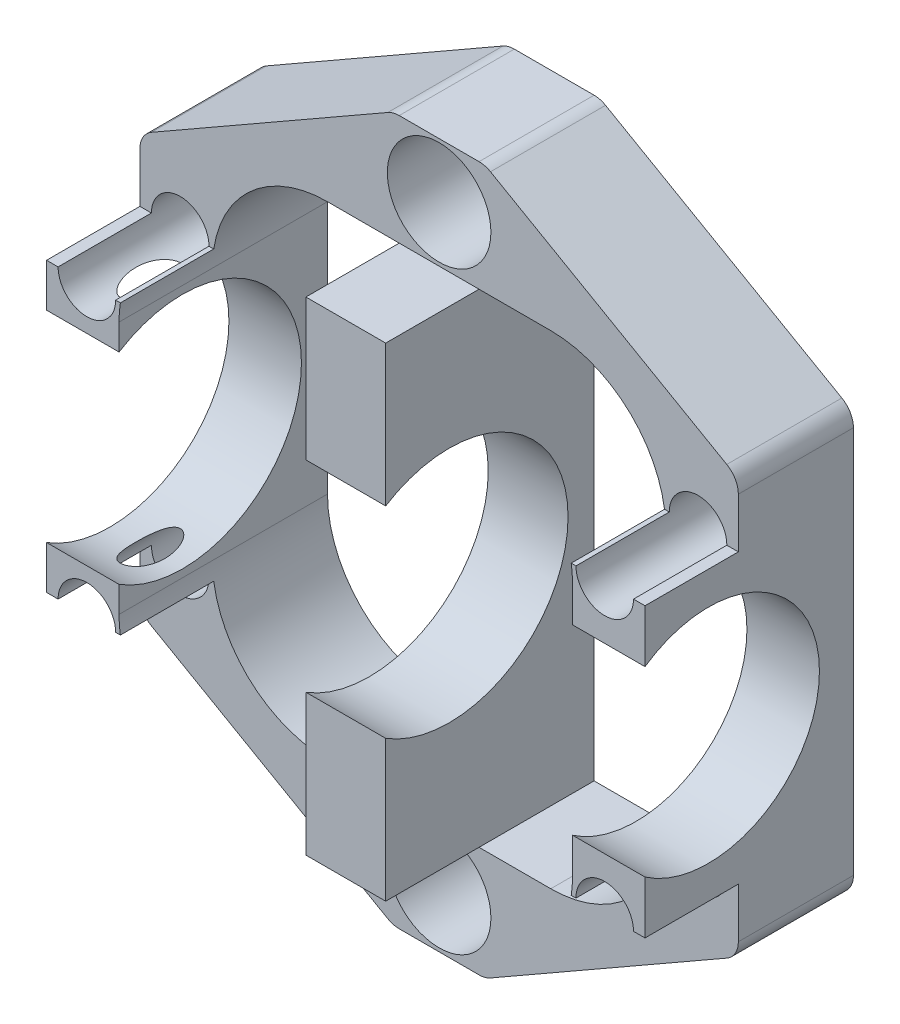
SolidWorks part; units mm, degrees
ref_plane "Front Plane" through (0, 0, 0) normal (0, 0, 1) x (1, 0, 0)
ref_plane "Top Plane" through (0, 0, 0) normal (0, 1, 0) x (1, 0, 0)
ref_plane "Right Plane" through (0, 0, 0) normal (1, 0, 0) x (0, 0, -1)
sketch "Sketch1" plane through (0, 0, 0) normal (0, 0, 1) x (1, 0, 0)
  line L0 (31.75, 34.925) -> (-31.75, 34.925) construction
  line L1 (-44.45, 22.225) -> (-44.45, -22.225) construction
  line L2 (-31.75, -34.925) -> (31.75, -34.925) construction
  line L3 (44.45, -22.225) -> (44.45, 22.225) construction
  line L4 (5.6665, -38.5261) -> (31.7424, -23.5917) construction
  line L5 (-33.02, -21.3876) -> (-33.02, 21.3876) construction
  line L6 (-31.7424, -23.5917) -> (-5.6665, -38.5261) construction
  line L7 (-4.4041, -38.862) -> (4.4041, -38.862) construction
  line L8 (33.02, -21.3876) -> (33.02, 21.3876) construction
  line L9 (5.6665, 38.5261) -> (31.7424, 23.5917) construction
  line L10 (-4.4041, 38.862) -> (4.4041, 38.862) construction
  line L11 (-5.6665, 38.5261) -> (-31.7424, 23.5917) construction
  line L12 (-33.02, -21.3876) -> (-33.02, 21.3876) construction
  line L13 (-33.02, -21.3876) -> (-33.02, 21.3876)
  line L14 (-5.6665, 38.5261) -> (-31.7424, 23.5917)
  line L15 (-4.4041, 38.862) -> (4.4041, 38.862)
  line L16 (5.6665, 38.5261) -> (31.7424, 23.5917)
  line L17 (33.02, -21.3876) -> (33.02, 21.3876)
  line L18 (-4.4041, -38.862) -> (4.4041, -38.862)
  line L19 (-31.7424, -23.5917) -> (-5.6665, -38.5261)
  line L20 (5.6665, -38.5261) -> (31.7424, -23.5917)
  line L21 (44.45, -22.225) -> (44.45, 22.225)
  line L22 (-31.75, -34.925) -> (31.75, -34.925)
  line L23 (-44.45, 22.225) -> (-44.45, -22.225)
  line L24 (31.75, 34.925) -> (-31.75, 34.925)
  line L25 (-12.319, 26.67) -> (12.319, 26.67) construction
  line L26 (25.019, 13.97) -> (25.019, -13.97) construction
  line L27 (-25.019, 13.97) -> (-25.019, -13.97) construction
  line L28 (-12.319, -26.67) -> (12.319, -26.67) construction
  line L29 (-12.319, 26.67) -> (12.319, 26.67)
  line L30 (25.019, 13.97) -> (25.019, -13.97)
  line L31 (-25.019, 13.97) -> (-25.019, -13.97)
  line L32 (-12.319, -26.67) -> (12.319, -26.67)
  line L33 (33.02, -15.875) -> (24.8753, -15.875)
  line L34 (33.02, 15.875) -> (24.8753, 15.875)
  line L35 (24.8753, 15.875) -> (24.8753, -15.875)
  line L36 (33.02, -15.875) -> (33.02, 15.875)
  line L37 (-33.02, -21.3876) -> (-33.02, 21.3876)
  line L38 (-33.02, -15.875) -> (-24.8753, -15.875)
  line L39 (-33.02, 15.875) -> (-24.8753, 15.875)
  line L40 (-33.02, 15.875) -> (-33.02, -15.875)
  line L41 (-24.8753, -15.875) -> (-24.8753, 15.875)
  line L42 (-4.4041, -38.862) -> (-4.4041, 38.862)
  line L43 (4.4041, -38.862) -> (4.4041, 38.862)
  line L44 (-12.319, 26.67) -> (12.319, 26.67) construction
  line L45 (-12.319, 26.67) -> (12.319, 26.67)
  arc A0 (-5.6665, -38.5261) -> (-4.4041, -38.862) centre (-4.4041, -36.322) ccw construction
  arc A1 (-31.75, 34.925) -> (-44.45, 22.225) centre (-31.75, 22.225) ccw construction
  arc A2 (-44.45, -22.225) -> (-31.75, -34.925) centre (-31.75, -22.225) ccw construction
  arc A3 (31.75, -34.925) -> (44.45, -22.225) centre (31.75, -22.225) ccw construction
  arc A4 (44.45, 22.225) -> (31.75, 34.925) centre (31.75, 22.225) ccw construction
  arc A5 (31.7424, -23.5917) -> (33.02, -21.3876) centre (30.48, -21.3876) ccw construction
  arc A6 (33.02, 21.3876) -> (31.7424, 23.5917) centre (30.48, 21.3876) ccw construction
  arc A7 (5.6665, 38.5261) -> (4.4041, 38.862) centre (4.4041, 36.322) ccw construction
  arc A8 (-4.4041, 38.862) -> (-5.6665, 38.5261) centre (-4.4041, 36.322) ccw construction
  arc A9 (-31.7424, 23.5917) -> (-33.02, 21.3876) centre (-30.48, 21.3876) ccw construction
  arc A10 (-33.02, -21.3876) -> (-31.7424, -23.5917) centre (-30.48, -21.3876) ccw construction
  arc A11 (-33.02, -21.3876) -> (-31.7424, -23.5917) centre (-30.48, -21.3876) ccw
  arc A12 (-31.7424, 23.5917) -> (-33.02, 21.3876) centre (-30.48, 21.3876) ccw
  arc A13 (-4.4041, 38.862) -> (-5.6665, 38.5261) centre (-4.4041, 36.322) ccw
  arc A14 (5.6665, 38.5261) -> (4.4041, 38.862) centre (4.4041, 36.322) ccw
  arc A15 (33.02, 21.3876) -> (31.7424, 23.5917) centre (30.48, 21.3876) ccw
  arc A16 (31.7424, -23.5917) -> (33.02, -21.3876) centre (30.48, -21.3876) ccw
  arc A17 (-5.6665, -38.5261) -> (-4.4041, -38.862) centre (-4.4041, -36.322) ccw
  arc A18 (44.45, 22.225) -> (31.75, 34.925) centre (31.75, 22.225) ccw
  arc A19 (31.75, -34.925) -> (44.45, -22.225) centre (31.75, -22.225) ccw
  arc A20 (-44.45, -22.225) -> (-31.75, -34.925) centre (-31.75, -22.225) ccw
  arc A21 (-31.75, 34.925) -> (-44.45, 22.225) centre (-31.75, 22.225) ccw
  arc A22 (-12.319, 26.67) -> (-25.019, 13.97) centre (-12.319, 13.97) ccw construction
  arc A23 (25.019, 13.97) -> (12.319, 26.67) centre (12.319, 13.97) ccw construction
  arc A24 (12.319, -26.67) -> (25.019, -13.97) centre (12.319, -13.97) ccw construction
  arc A25 (-25.019, -13.97) -> (-12.319, -26.67) centre (-12.319, -13.97) ccw construction
  arc A26 (-12.319, 26.67) -> (-25.019, 13.97) centre (-12.319, 13.97) ccw
  arc A27 (25.019, 13.97) -> (12.319, 26.67) centre (12.319, 13.97) ccw
  arc A28 (12.319, -26.67) -> (25.019, -13.97) centre (12.319, -13.97) ccw
  arc A29 (-25.019, -13.97) -> (-12.319, -26.67) centre (-12.319, -13.97) ccw
  circle A30 centre (0, -32.766) radius 5.715 construction
  circle A31 centre (0, 32.766) radius 5.715 construction
  circle A32 centre (-13.97, -15.875) radius 9.2075 construction
  circle A33 centre (-13.97, 15.875) radius 9.2075 construction
  circle A34 centre (13.97, 15.875) radius 9.2075 construction
  circle A35 centre (13.97, -15.875) radius 9.2075 construction
  circle A36 centre (0, -32.766) radius 5.715
  circle A37 centre (0, 32.766) radius 5.715
  circle A38 centre (-13.97, -15.875) radius 9.2075
  circle A39 centre (-13.97, 15.875) radius 9.2075
  circle A40 centre (13.97, 15.875) radius 9.2075
  circle A41 centre (13.97, -15.875) radius 9.2075
  arc A42 (4.4041, -38.862) -> (5.6665, -38.5261) centre (4.4041, -36.322) ccw construction
  arc A43 (4.4041, -38.862) -> (5.6665, -38.5261) centre (4.4041, -36.322) ccw
  circle A45 centre (-28.575, -15.875) radius 3.175 construction
  circle A46 centre (-28.575, -15.875) radius 3.175
  circle A47 centre (-28.575, 15.875) radius 3.175 construction
  circle A48 centre (-28.575, 15.875) radius 3.175
  circle A49 centre (28.575, -15.875) radius 3.175 construction
  circle A50 centre (28.575, -15.875) radius 3.175
  circle A51 centre (28.575, 15.875) radius 3.175 construction
  circle A52 centre (28.575, 15.875) radius 3.175
extrude "Boss-Extrude1" add sketch "Sketch1" along normal blind 12.7 contours L43 A43 L20 L22 A36 | A36 L42 L18 L43 | A50 L33 A28 L32 L43 A36 L22 L20 A16 L17 | A46 L38 L13 A11 L19 L22 A36 L42 L32 A29 | A36 L22 L19 A17 L42 | A36 L43 L32 L42 | A52 L34 L17 A15 L16 L24 A37 L43 L29 A27 | A37 L24 L16 A14 L43 | A37 L43 L15 L42 | A48 L39 A26 L29 L42 A37 L24 L14 A12 L13 | A37 L42 A13 L14 L24 | A37 L42 L29 L43 region at (-18.724, -26.6283, 0) region at (-18.724, 26.6283, 0) region at (-7.0498, -36.3818, 0) region at (-4.3127, -37.635, 0) region at (-4.3127, -27.897, 0) region at (-7.0498, 36.3818, 0) region at (7.0498, -36.3818, 0) region at (18.724, -26.6283, 0) region at (-4.3127, 27.897, 0) region at (0, 38.7706, 0) region at (18.724, 26.6283, 0) region at (7.0498, 36.3818, 0)
extrude "Boss-Extrude3" add sketch "Sketch1<4>" along normal blind 23 contours A52 L34 A27 L30 A28 L33 A50 L17 | A48 L39 L37 L38 A46 A29 L31 A26 | L32 L43 L29 L42 region at (-29.0794, 0, 0) region at (0, 0, 0) region at (29.0794, 0, 0)
sketch "Sketch1<4>" plane through (0, 0, 0) normal (0, 0, 1) x (1, 0, 0) same geometry as "Sketch1"
sketch "Sketch8" plane through (33.02, 0, 0) normal (1, 0, 0) x (0, 0, -1)
  line L0 (-1000, 0) -> (49000, 0) construction
  line L1 (0, -21.3876) -> (0, 21.3876) construction
  circle A0 centre (-16, 0) radius 12.25
  point P5 (0, 0)
  dimension "D1" = 24.5
  dimension "D2" = 16
sketch "Sketch9" plane through (-33.02, 0, 0) normal (-1, 0, 0) x (0, 0, 1)
  line L0 (-1000, 0) -> (49000, 0) construction
  line L1 (0, -21.3876) -> (0, 21.3876) construction
  circle A0 centre (16, 0) radius 13.125
  point P5 (0, 0)
  dimension "D2" = 16
  dimension "D1" = 26.25
extrude "Cut-Extrude3" cut sketch "Sketch9" against normal up to surface (37.4241 mm away) up to face at (4.4041, 0, 11.9)
extrude "Cut-Extrude4" cut sketch "Sketch8" against normal up to next
equation "\"shaftLength\"= 143"
equation "\"shaftMaxDiameter\"= 26.25"
equation "\"shaftMinDiameter\"= 24.5"
equation "\"knobSmallDiameter\" = 13"
equation "\"knobLargeDiameter\" = 27"
equation "\"postKnobCatheterConnection\" = 12.5"
equation "\"servoHexagonDiameter\" = 15"
equation "\"servoHexagonArmThickness\" = 2.2"
equation "\"servoHexagonHeight\" = 20"
equation "\"servoHexagonSeparation\" = 33"
equation "\"servoCylinderDiameter\" = 8"
equation "\"aurisSheathHeight\" = 16"
equation "\"platformWidth\" = 60"
equation "\"platformLength\" = 60"
equation "\"frontCylinderLength\" = 10"
equation "\"D1@Sketch2\"=\"shaftMinDiameter\""
equation "\"D2@Sketch2\"=\"aurisSheathHeight\""
equation "\"D1@Sketch3\"=\"shaftMaxDiameter\""
equation "\"D2@Sketch3\"=\"aurisSheathHeight\""
equation "\"D1@Sketch8\"=\"shaftMinDiameter\""
equation "\"D2@Sketch8\"=\"aurisSheathHeight\""
equation "\"D1@Sketch9\"=\"shaftMaxDiameter\""
equation "\"D2@Sketch9\"=\"aurisSheathHeight\""
